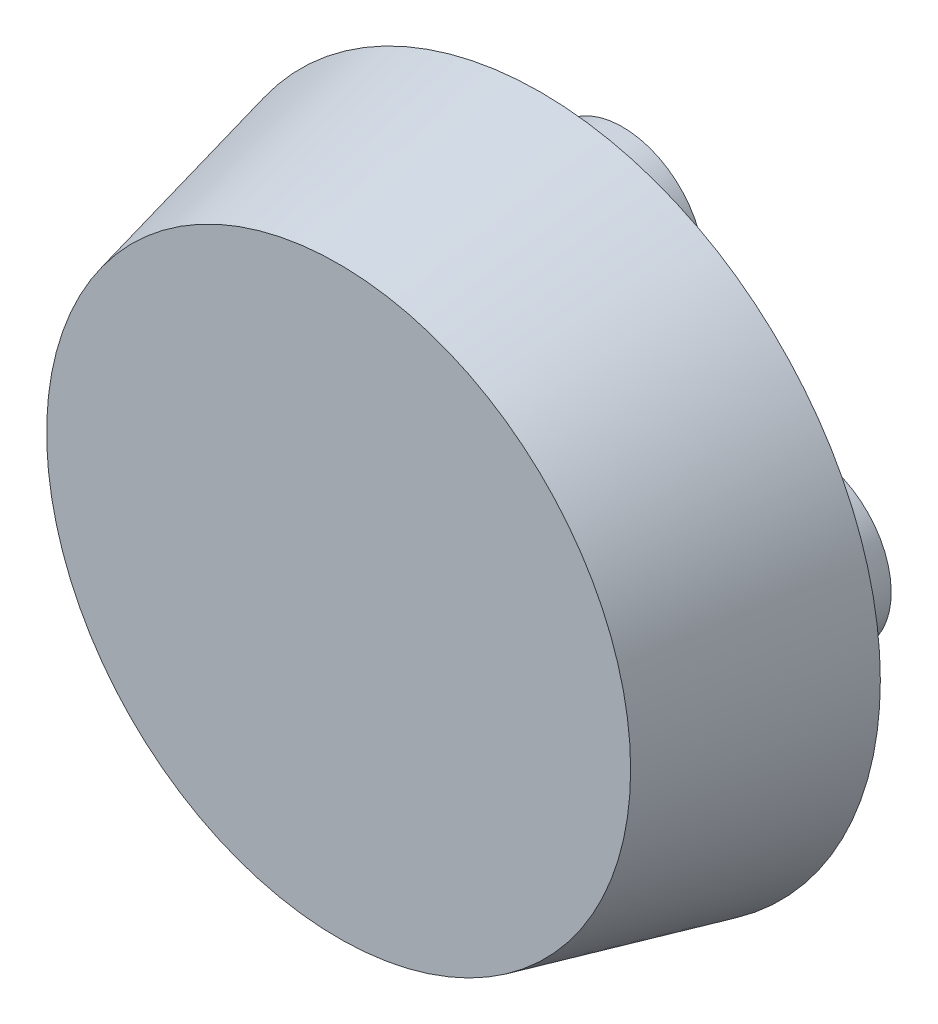
SolidWorks part; units mm, degrees
ref_plane "Front Plane" through (0, 0, 0) normal (0, 0, 1) x (1, 0, 0)
ref_plane "Top Plane" through (0, 0, 0) normal (0, 1, 0) x (1, 0, 0)
ref_plane "Right Plane" through (0, 0, 0) normal (1, 0, 0) x (0, 0, -1)
sketch "Big Plug Sketch" plane through (0, 0, 0) normal (1, 0, 0) x (0, 0, -1)
  line L0 (594.1751, -558.8643) -> (886.5863, -558.8643) construction
  line L1 (0, 0) -> (531.6016, 125) construction
  line L2 (0, 0) -> (531.6016, 0) construction
  line L3 (531.6016, 125) -> (531.6016, 0)
  line L4 (531.6016, 125) -> (618.1413, 145.3488)
  line L5 (531.6016, 0) -> (635, 0)
  arc A1 (635, 0) -> (618.1413, 145.3488) centre (0, 0) ccw
  dimension "D1" = 546.1
  dimension "D2" = 635
  dimension "D3" = 125
revolve "Big Plug" add sketch "Big Plug Sketch" angle 360 about L2
ref_plane "Big Plug Subsurface Plane" through (0, 0, -618.1413) normal (0, 0, 1) x (1, 0, 0)
sketch "Cable Sketch" plane through (0, 0, -618.1413) normal (0, 0, 1) x (1, 0, 0)
  line L0 (0, 80) -> (0, 0) construction
  circle A0 centre (0, 80) radius 35
  dimension "D1" = 70
  dimension "D2" = 80
extrude "Cable Extrude" add sketch "Cable Sketch" against normal blind 35
pattern_circular "Cable Pattern" count 4 over 360 about axis through (0, 0, -531.6016) along (0, 0, -1) of "Cable Extrude"
